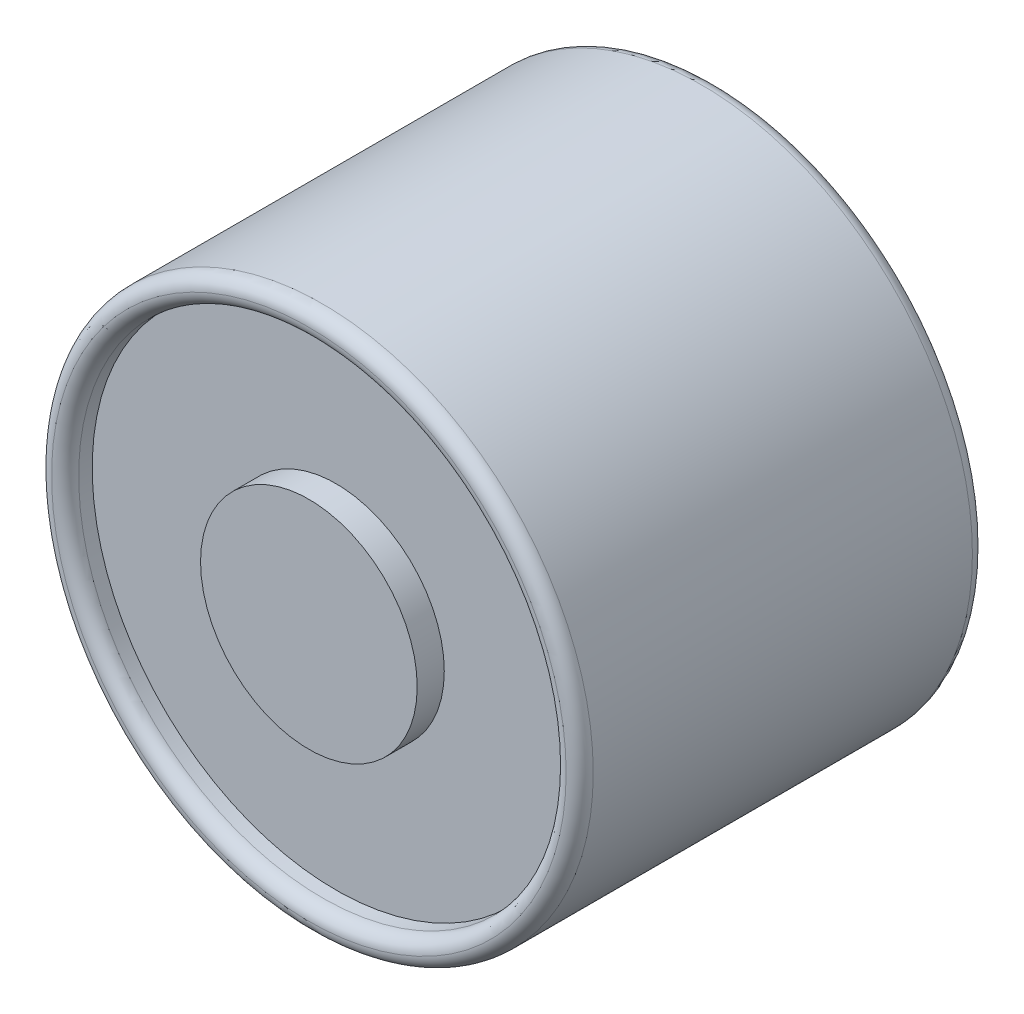
SolidWorks part; units mm, degrees
ref_plane "前视基准面" through (0, 0, 0) normal (0, 0, 1) x (1, 0, 0)
ref_plane "上视基准面" through (0, 0, 0) normal (0, 1, 0) x (1, 0, 0)
ref_plane "右视基准面" through (0, 0, 0) normal (1, 0, 0) x (0, 0, -1)
sketch "草图1" plane through (0, 0, 0) normal (0, 0, 1) x (1, 0, 0)
  circle A0 centre (0, 0) radius 10
extrude "凸台-拉伸1" add sketch "草图1" along normal blind 15
sketch "草图2" plane through (0, 0, 15) normal (0, 0, 1) x (1, 0, 0)
  circle A0 centre (0, 0) radius 4
  circle A1 centre (0, 0) radius 9
extrude "切除-拉伸1" cut sketch "草图2" against normal blind 1
fillet "圆角1" radius 0.5 3 edges at (10, 0, 0) (9, 0, 15) (10, 0, 15)
sketch "草图3" plane through (0, 0, 0) normal (0, 0, -1) x (-1, 0, 0)
  circle A0 centre (0, 0) radius 2
extrude "切除-拉伸2" cut sketch "草图3" against normal blind 8
